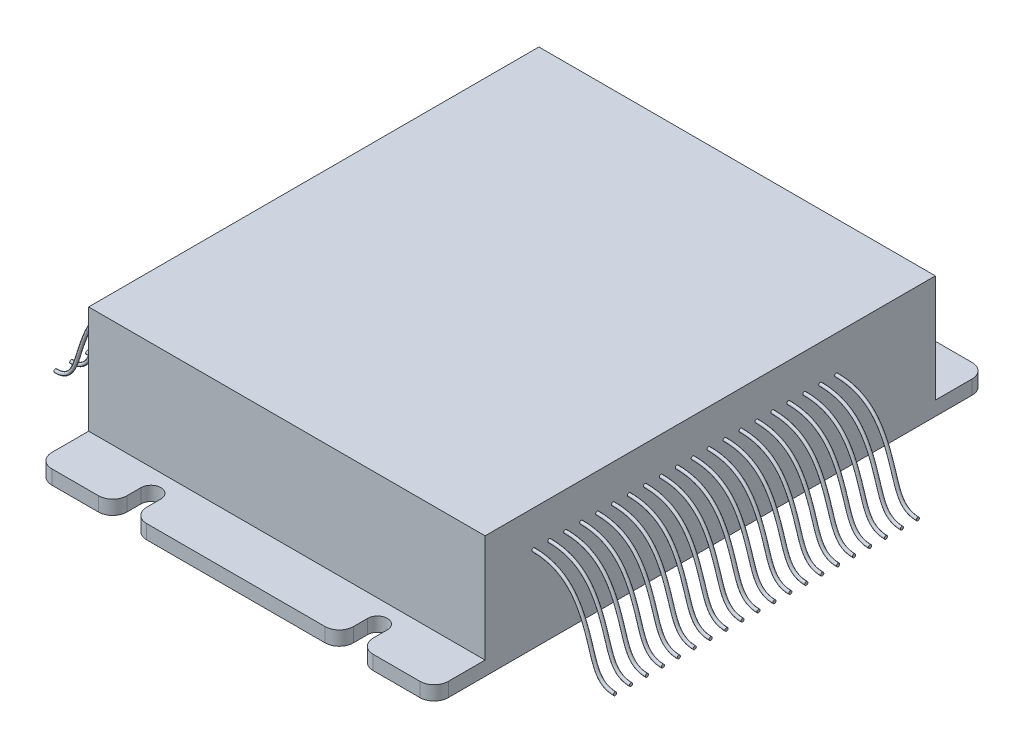
SolidWorks part; units mm, degrees
ref_plane "Front Plane" through (0, 0, 0) normal (0, 0, 1) x (1, 0, 0)
ref_plane "Top Plane" through (0, 0, 0) normal (0, 1, 0) x (1, 0, 0)
ref_plane "Right Plane" through (0, 0, 0) normal (1, 0, 0) x (0, 0, -1)
sketch "Sketch1" plane through (0, 0, 0) normal (0, 1, 0) x (1, 0, 0)
  line L0 (-11.049, 22.225) -> (-11.049, 23.495)
  line L1 (-16.51, 24.765) -> (-12.319, 24.765)
  line L2 (-17.78, 23.495) -> (-17.78, -23.495)
  line L3 (-16.51, -24.765) -> (-12.319, -24.765)
  line L4 (17.78, 23.495) -> (17.78, -23.495)
  line L5 (-17.78, 24.765) -> (17.78, -24.765) construction
  line L6 (-17.78, -24.765) -> (17.78, 24.765) construction
  line L7 (-9.271, 22.225) -> (-9.271, 23.495)
  line L8 (-8.001, 24.765) -> (8.001, 24.765)
  line L9 (0, -55) -> (0, 55) construction
  line L10 (9.271, 22.225) -> (9.271, 23.495)
  line L11 (11.049, 22.225) -> (11.049, 23.495)
  line L12 (-55, 0) -> (55, 0) construction
  line L13 (11.049, -22.225) -> (11.049, -23.495)
  line L14 (9.271, -22.225) -> (9.271, -23.495)
  line L15 (-9.271, -22.225) -> (-9.271, -23.495)
  line L16 (-11.049, -22.225) -> (-11.049, -23.495)
  line L17 (12.319, 24.765) -> (16.51, 24.765)
  line L18 (-8.001, -24.765) -> (8.001, -24.765)
  line L19 (12.319, -24.765) -> (16.51, -24.765)
  arc A0 (-11.049, 22.225) -> (-9.271, 22.225) centre (-10.16, 22.225) ccw
  arc A1 (16.51, -24.765) -> (17.78, -23.495) centre (16.51, -23.495) ccw
  arc A2 (-17.78, -23.495) -> (-16.51, -24.765) centre (-16.51, -23.495) ccw
  arc A3 (16.51, 24.765) -> (17.78, 23.495) centre (16.51, 23.495) cw
  arc A4 (-16.51, 24.765) -> (-17.78, 23.495) centre (-16.51, 23.495) ccw
  arc A5 (-9.271, 23.495) -> (-8.001, 24.765) centre (-8.001, 23.495) cw
  arc A6 (-11.049, 23.495) -> (-12.319, 24.765) centre (-12.319, 23.495) ccw
  arc A7 (9.271, 23.495) -> (8.001, 24.765) centre (8.001, 23.495) ccw
  arc A8 (11.049, 22.225) -> (9.271, 22.225) centre (10.16, 22.225) cw
  arc A9 (11.049, 23.495) -> (12.319, 24.765) centre (12.319, 23.495) cw
  arc A10 (11.049, -23.495) -> (12.319, -24.765) centre (12.319, -23.495) ccw
  arc A11 (11.049, -22.225) -> (9.271, -22.225) centre (10.16, -22.225) ccw
  arc A12 (9.271, -23.495) -> (8.001, -24.765) centre (8.001, -23.495) cw
  arc A13 (-11.049, -23.495) -> (-12.319, -24.765) centre (-12.319, -23.495) cw
  arc A14 (-9.271, -23.495) -> (-8.001, -24.765) centre (-8.001, -23.495) ccw
  arc A15 (-11.049, -22.225) -> (-9.271, -22.225) centre (-10.16, -22.225) cw
  point P0 (0, 0)
  point P25 (-9.271, 24.765)
  point P60 (0, 0)
  dimension "D3" = 1.778
  dimension "D6" = 1.27
  dimension "D1" = 35.56
  dimension "D2" = 49.53
  dimension "D4" = 2.54
  dimension "D5" = 7.62
extrude "Boss-Extrude1" add sketch "Sketch1" along normal blind 1.27
sketch "Sketch2" plane through (0, 1.27, 0) normal (0, 1, 0) x (1, 0, 0)
  line L0 (17.78, -23.495) -> (17.78, 23.495) construction
  line L1 (-17.78, 20.193) -> (17.78, 20.193)
  line L2 (-17.78, 20.193) -> (-17.78, -20.193)
  line L3 (-17.78, -20.193) -> (17.78, -20.193)
  line L4 (17.78, 20.193) -> (17.78, -20.193)
  line L5 (-17.78, 20.193) -> (17.78, -20.193) construction
  line L6 (-17.78, -20.193) -> (17.78, 20.193) construction
  point P0 (0, 0)
  dimension "D1" = 40.386
extrude "Boss-Extrude2" add sketch "Sketch2" along normal blind 9.652
ref_plane "Plane1" through (0, 0, 16.002) normal (0, 0, 1) x (1, 0, 0)
sketch "Sketch3" plane through (0, 0, 16.002) normal (0, 0, 1) x (1, 0, 0)
  line L0 (-17.78, 1.27) -> (-17.78, 0) construction
  line L1 (-17.78, 10.922) -> (17.78, 10.922) construction
  line L2 (-27.7125, 0) -> (-23.9431, 0) construction
  line L3 (-17.78, 7.5311) -> (-20.7776, 7.5311) construction
  spline S0 degree 3 poles (-17.78, 7.5311) (-21.172, 7.5311) (-22.5259, 3.6578) (-23.608, 0) (-25.1003, 0) knots 0 0 0 0 0.668189 1 1 1 1
  point P2 (-22.3465, 1.6167)
  dimension "D1" = 3.3909
  dimension "D2" = 7.3203
  dimension "D3" = 5.08
  dimension "D4" = 5.08
  dimension "D5" = 1.27
ref_plane "Plane2" through (-25.1003, 0, 0) normal (-1, 0, 0) x (0, 0, 1)
sketch "Sketch4" plane through (-25.1003, 0, 0) normal (-1, 0, 0) x (0, 0, 1)
  line L0 (16.002, 0) -> (16.002, 7.5311) construction
  line L3 (-23.495, 0) -> (23.495, 0) construction
  circle A0 centre (15.8587, 0.1433) radius 0.1433
  point P4 (15.2908, 1.1362)
  dimension "D1" = 0.2865
sweep "Sweep1" add profiles "Sketch4" path "Sketch3"
pattern_linear "LPattern1" count 20 spacing 1.4295 along (0, 0, -1) of "Sweep1"
mirror "Mirror1" about plane through (0, 0, 0) normal (1, 0, 0) of "LPattern1", "Sweep1"
